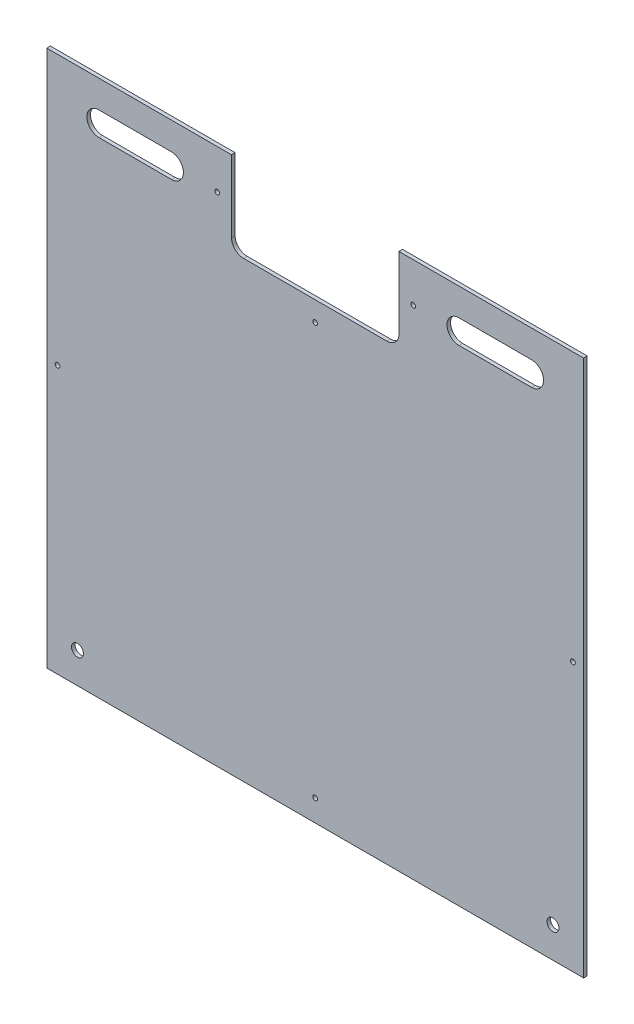
SolidWorks part; units mm, degrees
ref_plane "Piano frontale" through (0, 0, 0) normal (0, 0, 1) x (1, 0, 0)
ref_plane "Piano superiore" through (0, 0, 0) normal (0, 1, 0) x (1, 0, 0)
ref_plane "Piano destro" through (0, 0, 0) normal (1, 0, 0) x (0, 0, -1)
sketch "Schizzo1" plane through (0, 0, 0) normal (0, 0, 1) x (1, 0, 0)
  line L0 (0, 0) -> (0, 449)
  line L1 (0, 449) -> (154.5, 449)
  line L2 (449, 449) -> (449, 0)
  line L3 (449, 0) -> (0, 0)
  line L4 (154.5, 449) -> (154.5, 389)
  line L5 (164.5, 379) -> (284.5, 379)
  line L6 (294.5, 389) -> (294.5, 449)
  line L7 (294.5, 449) -> (449, 449)
  line L8 (154.5, 415.9998) -> (294.5, 415.9998) construction
  line L9 (224.5, 379) -> (224.5, 419) construction
  line L10 (344.7159, 415.9998) -> (405.4404, 415.9998) construction
  line L11 (344.7159, 425.9998) -> (405.4404, 425.9998)
  line L12 (344.7159, 405.9998) -> (405.4404, 405.9998)
  line L13 (104.2841, 415.9998) -> (43.5596, 415.9998) construction
  line L14 (104.2841, 425.9998) -> (43.5596, 425.9998)
  line L15 (104.2841, 405.9998) -> (43.5596, 405.9998)
  line L16 (0, 0) -> (224.5, 224.5) construction
  line L17 (224.5, 224.5) -> (449, 0) construction
  arc A0 (154.5, 389) -> (164.5, 379) centre (164.5, 389) ccw
  arc A1 (294.5, 389) -> (284.5, 379) centre (284.5, 389) cw
  circle A2 centre (142.5666, 415.9998) radius 2
  circle A3 centre (224.5, 362.449) radius 2
  circle A4 centre (306.4334, 415.9998) radius 2
  circle A5 centre (9, 223.8264) radius 2
  circle A6 centre (440, 224.5) radius 2
  circle A7 centre (224.5, 18.1468) radius 2
  arc A8 (344.7159, 425.9998) -> (344.7159, 405.9998) centre (344.7159, 415.9998) ccw
  arc A9 (405.4404, 405.9998) -> (405.4404, 425.9998) centre (405.4404, 415.9998) ccw
  arc A10 (104.2841, 425.9998) -> (104.2841, 405.9998) centre (104.2841, 415.9998) cw
  arc A11 (43.5596, 405.9998) -> (43.5596, 425.9998) centre (43.5596, 415.9998) cw
  circle A12 centre (25.7025, 25.7025) radius 5
  circle A13 centre (423.2975, 25.7025) radius 5
  point P11 (154.5, 379)
  point P14 (294.5, 379)
  point P33 (375.0781, 415.9998)
  point P40 (73.9219, 415.9998)
  dimension "D5" = 10
  dimension "D6" = 4
  dimension "D7" = 4
  dimension "D8" = 4
  dimension "D9" = 4
  dimension "D10" = 4
  dimension "D12" = 10
  dimension "D1" = 449
  dimension "D2" = 449
  dimension "D3" = 140
  dimension "D4" = 70
  dimension "D11" = 20
  dimension "D13" = 9
  dimension "D14" = 9
extrude "Estrusione-Estrusione1" add sketch "Schizzo1" along normal blind 3
